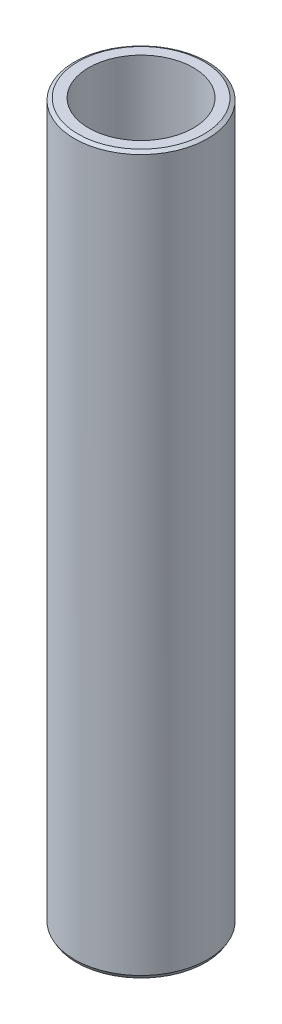
SolidWorks part; units mm, degrees
ref_plane "Front Plane" through (0, 0, 0) normal (0, 0, 1) x (1, 0, 0)
ref_plane "Top Plane" through (0, 0, 0) normal (0, 1, 0) x (1, 0, 0)
ref_plane "Right Plane" through (0, 0, 0) normal (1, 0, 0) x (0, 0, -1)
sketch "Sketch1" plane through (0, 0, 0) normal (0, 1, 0) x (1, 0, 0)
  circle A0 centre (0, 0) radius 45
  dimension "SHAFT_OD" = 90
extrude "Boss-Extrude1" add sketch "Sketch1" along normal blind 484.6593
sketch "Sketch2" plane through (0, 0, 0) normal (0, 1, 0) x (1, 0, 0)
  circle A0 centre (0, 0) radius 35.4088
  dimension "BORE_D" = 70.8175
extrude "Cut-Extrude1" cut sketch "Sketch2" along normal through all
chamfer "Chamfer1" distance 1.4284 angle 60 2 edges at (0, 484.6593, 45) (0, 0, 45) first distance on face at (0, 484.6593, 45) first distance on face at (0, 0, 35.4088)
